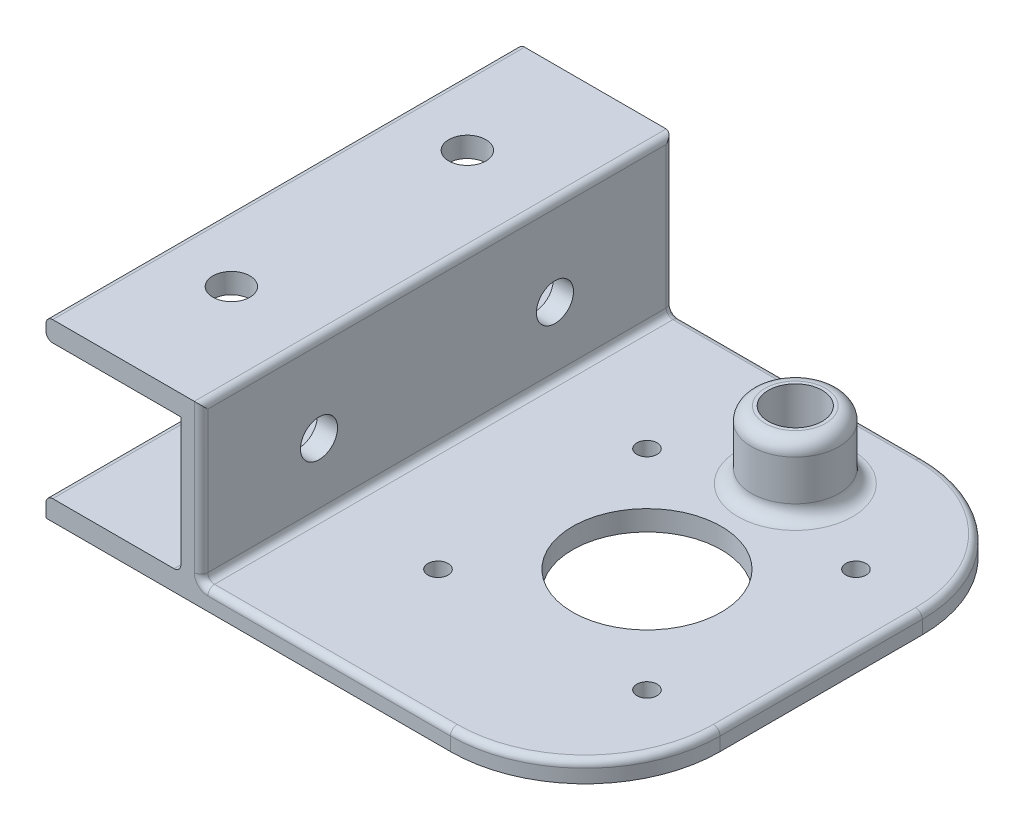
SolidWorks part; units mm, degrees
ref_plane "Front Plane" through (0, 0, 0) normal (0, 0, 1) x (1, 0, 0)
ref_plane "Top Plane" through (0, 0, 0) normal (0, 1, 0) x (1, 0, 0)
ref_plane "Right Plane" through (0, 0, 0) normal (1, 0, 0) x (0, 0, -1)
sketch "Sketch1" plane through (0, 0, 0) normal (0, 1, 0) x (1, 0, 0)
  line L1 (-40, -35) -> (40, -35)
  line L2 (-40, -35) -> (-40, 35)
  line L3 (-40, 35) -> (40, 35)
  line L4 (40, -35) -> (40, 35)
  line L5 (-40, -35) -> (40, 35) construction
  line L6 (-40, 35) -> (40, -35) construction
  line L7 (-20, 35) -> (-17, 35)
  line L8 (-20, 35) -> (-20, -35)
  line L9 (-20, -35) -> (-17, -35)
  line L10 (-17, 35) -> (-17, -35)
  circle A0 centre (-30, 17.5) radius 2.5
  circle A1 centre (-30, -17.5) radius 2.5
  point P0 (0, 0)
  dimension "D7" = 5
  dimension "D8" = 5
  dimension "D1" = 80
  dimension "D2" = 70
  dimension "D3" = 17.5
  dimension "D4" = 17.5
  dimension "D5" = 10
  dimension "D6" = 10
  dimension "D9" = 20
  dimension "D10" = 3
extrude "Boss-Extrude1" add sketch "Sketch1" along normal blind 3 contours L8 L3 L2 L1 A1 A0 | L3 L10 L1 L4 | L10 L3 L8 L1 region at (-30, 0, 0) region at (-18.5, 0, 0) region at (11.5, 0, 0)
extrude "Boss-Extrude2" add sketch "Sketch1<3>" along normal blind 26 contours L10 L3 L8 L1 region at (-18.5, 0, 0)
sketch "Sketch1<3>" plane through (0, 0, 0) normal (0, 1, 0) x (1, 0, 0) same geometry as "Sketch1"
sketch "Sketch2" plane through (-17, 0, 0) normal (1, 0, 0) x (0, 0, -1)
  line L0 (-35, 3) -> (-35, 23)
  line L1 (-35, 26) -> (-35, 3) construction
  line L2 (-35, 23) -> (35, 23)
  line L3 (35, 26) -> (35, 3) construction
  line L4 (35, 23) -> (35, 3)
  line L5 (35, 3) -> (-35, 3)
  circle A0 centre (-17.5, 13) radius 2.5
  circle A1 centre (17.5, 13) radius 2.5
  point P14 (0, 3)
  point P16 (-35, 13)
  dimension "D4" = 5
  dimension "D5" = 5
  dimension "D1" = 20
  dimension "D2" = 17.5
  dimension "D3" = 17.5
extrude "Cut-Extrude1" cut sketch "Sketch2" against normal blind 17 contours A0 | A1
sketch "Sketch3" plane through (0, 3, 0) normal (0, 1, 0) x (1, 0, 0)
  line L0 (-17, -35) -> (-17, 35) construction
  line L1 (-7, -21.15) -> (35.3, -21.15)
  line L2 (-7, -21.15) -> (-7, 21.15)
  line L3 (-7, 21.15) -> (35.3, 21.15)
  line L4 (35.3, -21.15) -> (35.3, 21.15)
  line L5 (-7, -21.15) -> (35.3, 21.15) construction
  line L6 (-7, 21.15) -> (35.3, -21.15) construction
  line L7 (-7, 0) -> (35.3, 0) construction
  line L8 (14.15, 21.15) -> (14.15, -21.15) construction
  circle A3 centre (14.15, 0) radius 11.025
  circle A4 centre (29.65, 15.5) radius 1.5
  circle A5 centre (-1.35, 15.5) radius 1.5
  circle A6 centre (-1.35, -15.5) radius 1.5
  circle A7 centre (29.65, -15.5) radius 1.5
  point P11 (-7, 0)
  point P14 (-17, 0)
  dimension "D7" = 3
  dimension "D11" = 3
  dimension "D12" = 3
  dimension "D13" = 3
  dimension "D14" = 22.05
  dimension "D2" = 31
  dimension "D3" = 31
  dimension "D4" = 0
  dimension "D5" = 31
  dimension "D6" = 31
  dimension "D8" = 42.3
  dimension "D9" = 42.3
  dimension "D10" = 10
extrude "Cut-Extrude2" cut sketch "Sketch3" against normal blind 10 contours A5 | A3 | A4 | A7 | A6 region at (14.15, 3, 0) region at (29.65, 3, -15.5) region at (-1.35, 3, -15.5) region at (-1.35, 3, 15.5) region at (29.65, 3, 15.5)
fillet "Fillet1" radius 20 2 edges at (40, 1.5, 35) (40, 1.5, -35)
extrude "Boss-Extrude4" add sketch "Sketch1<4>" against normal blind 3 from surface contours L8 L3 L2 L1 A1 A0 region at (-30, 0, 0) starting at face at (-18.5, 26, 0)
sketch "Sketch1<4>" plane through (0, 0, 0) normal (0, 1, 0) x (1, 0, 0) same geometry as "Sketch1"
sketch "Sketch4" plane through (0, 3, 0) normal (0, 1, 0) x (1, 0, 0)
  circle A0 centre (14.15, 22) radius 4
  circle A1 centre (14.15, 22) radius 6.5
  point P5 (14.15, 0)
  dimension "D1" = 8
  dimension "D2" = 13
  dimension "D3" = 22
extrude "Boss-Extrude5" add sketch "Sketch4" along normal blind 10
fillet "Fillet2" radius 1 13 edges at (-17, 14.5, -35) (-17, 14.5, 35) (1.5, 3, -35) (34.1421, 3, -29.1421) (40, 3, 0) (34.1421, 3, 29.1421) (-17, 26, 0) (-17, 3, 0) (1.5, 3, 35) (-20, 3, 0) (-40, 23, 0) (-40, 3, 0) (-40, 26, 0)
fillet "Fillet3" radius 2 2 edges at (14.15, 3, -15.5) (14.15, 13, -15.5)
hole_wizard "M5 Clearance Hole1" positions "Sketch5" profile "Sketch6" hole size "M5" standard "ANSI Metric" end condition through all
sketch "Sketch5" plane through (-17, 0, 0) normal (1, 0, 0) x (0, 0, -1)
  point P0 (-17.5, 13)
  point P3 (17.5, 13)
sketch "Sketch6" plane through (-17, 13, 17.5) normal (0, 1, 0) x (0, 0, -1)
  line L0 (0, 0) -> (0, 23)
  line L1 (0, 23) -> (2.75, 23)
  line L2 (2.75, 23) -> (2.75, 0)
  line L5 (2.75, 0) -> (0, 0)
  line L11 (0, -6.35) -> (0, 107.95) construction
  dimension "Thru Hole Dia." = 5.5
  dimension "Thru Hole Depth" = 23
hole_wizard "M5 Clearance Hole2" positions "Sketch7" profile "Sketch8" hole size "M5" standard "ANSI Metric" end condition through all
sketch "Sketch7" plane through (0, 26, 0) normal (0, 1, 0) x (1, 0, 0)
  point P0 (-30, -17.5)
  point P3 (-30, 17.5)
sketch "Sketch8" plane through (-30, 26, 17.5) normal (1, 0, 0) x (0, 0, 1)
  line L0 (0, 0) -> (0, 26)
  line L1 (0, 26) -> (2.75, 26)
  line L2 (2.75, 26) -> (2.75, 0)
  line L5 (2.75, 0) -> (0, 0)
  line L11 (0, -6.35) -> (0, 107.95) construction
  dimension "Thru Hole Dia." = 5.5
  dimension "Thru Hole Depth" = 26
